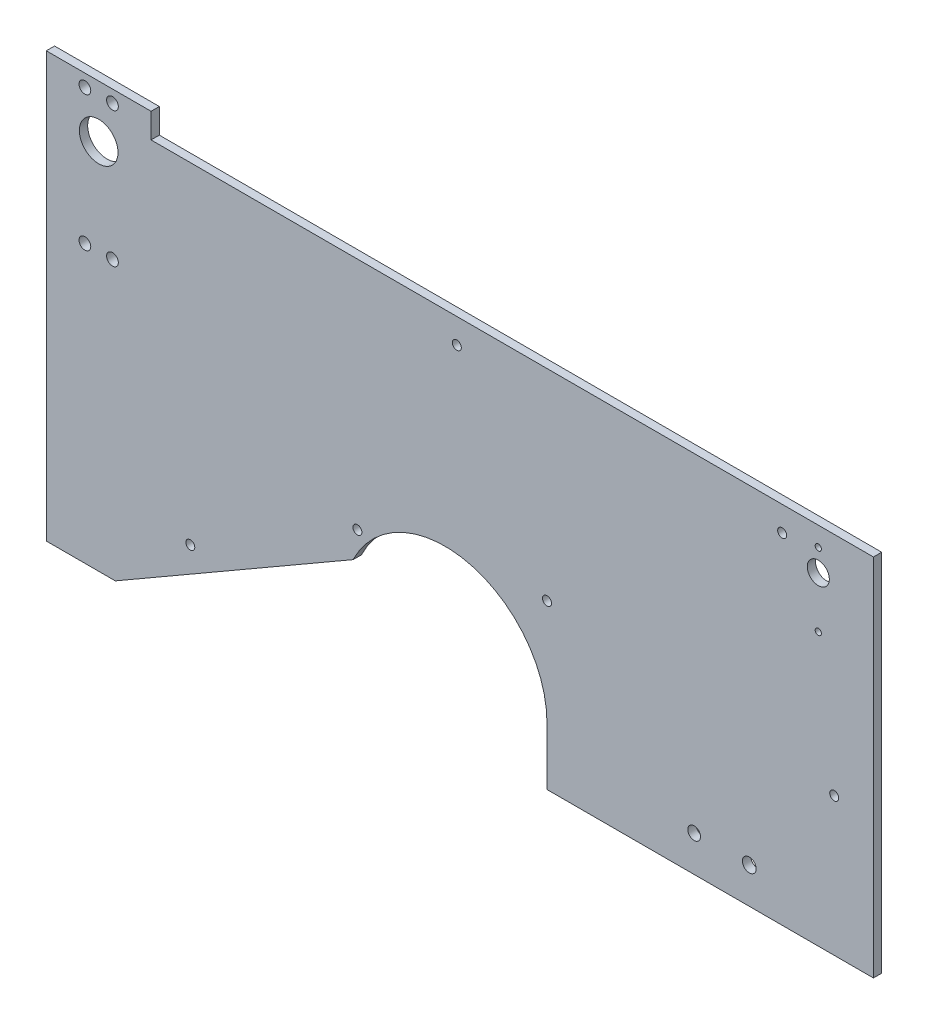
SolidWorks part; units mm, degrees
ref_plane "Front Plane" through (0, 0, 0) normal (0, 0, 1) x (1, 0, 0)
ref_plane "Top Plane" through (0, 0, 0) normal (0, 1, 0) x (1, 0, 0)
ref_plane "Right Plane" through (0, 0, 0) normal (1, 0, 0) x (0, 0, -1)
sketch "Sketch2" plane through (0, 0, 0) normal (0, 0, 1) x (1, 0, 0)
  line L0 (25.0304, 0) -> (111.2865, 49.8)
  line L1 (0, 0) -> (25.0304, 0)
  line L2 (0, 0) -> (0, 154)
  line L4 (300, 0) -> (300, 145)
  line L5 (181.6, 33.7) -> (181.6, 0)
  line L6 (181.6, 0) -> (300, 0)
  line L7 (19, 135) -> (19, 164.3674) construction
  line L11 (38, 145) -> (300, 145)
  line L12 (0, 154) -> (19, 154)
  line L13 (19, 154) -> (38, 154)
  line L14 (38, 154) -> (38, 145)
  line L15 (19, 135) -> (50019, 135) construction
  line L20 (19, 135) -> (19, -49865) construction
  line L21 (24, 149.5) -> (24, -49850.5) construction
  line L22 (14, 149.5) -> (14, -49850.5) construction
  circle A0 centre (19, 135) radius 7
  arc A1 (181.6, 33.7) -> (111.2865, 49.8) centre (144.6, 33.7) ccw
  circle A2 centre (14, 149.5) radius 2.125
  circle A3 centre (24, 149.5) radius 2.125
  circle A4 centre (24, 100.5) radius 2.125
  circle A5 centre (14, 100.5) radius 2.125
  point P19 (19, 154)
  dimension "D3" = 135
  dimension "D4" = 19
  dimension "D5" = 14
  dimension "D6" = 74
  dimension "D7" = 155.4
  dimension "D8" = 33.7
  dimension "D13" = 4.25
  dimension "D14" = 5
  dimension "D15" = 14.5
  dimension "D17" = 49
  dimension "D18" = 4.25
  dimension "D19" = 49
  dimension "D20" = 4.25
  dimension "D1" = 300
  dimension "D2" = 154
  dimension "D9" = 30
  dimension "D10" = 99.6
  dimension "D11" = 19
  dimension "D12" = 145
  dimension "D16" = 9
extrude "Boss-Extrude2" add sketch "Sketch2" along normal blind 3
sketch "Sketch3" plane through (0, 0, 3) normal (0, 0, 1) x (1, 0, 0)
  line L0 (300, 0) -> (300, 145) construction
  line L1 (181.6, 0) -> (300, 0)
  line L2 (181.6, 0) -> (181.6, 12.75)
  line L3 (181.6, 12.75) -> (300, 12.75)
  line L4 (300, 0) -> (300, 12.75)
  dimension "D1" = 12.75
extrude "Cut-Extrude1" cut sketch "Sketch3" against normal through all
sketch "Sketch4" plane through (0, 0, 3) normal (0, 0, 1) x (1, 0, 0)
  line L0 (19, 135) -> (19, -49865) construction
  line L1 (19, 135) -> (-49981, 135) construction
sketch "Sketch5" plane through (0, 0, 3) normal (0, 0, 1) x (1, 0, 0)
  line L0 (300, 12.75) -> (300, 145) construction
  line L1 (300, 12.75) -> (181.6, 12.75) construction
  line L2 (300, 145) -> (38, 145) construction
  line L3 (0, 154) -> (0, 0) construction
  line L4 (0, 0) -> (25.0304, 0) construction
  circle A0 centre (254.98, 25.75) radius 2.5
  circle A1 centre (234.98, 25.75) radius 2.3061
  circle A2 centre (280, 130) radius 4
  circle A3 centre (280, 138) radius 1.125
  circle A4 centre (280, 111.5) radius 1.125
  circle A7 centre (285.78, 62.92) radius 1.625
  circle A8 centre (181.6, 72.03) radius 1.625
  circle A9 centre (52.23, 24.91) radius 1.625
  circle A10 centre (112.84, 59.93) radius 1.625
  circle A11 centre (266.895, 135.995) radius 1.625
  circle A12 centre (148.895, 135.995) radius 1.625
  dimension "D1" = 45.02
  dimension "D2" = 13
  dimension "D3" = 20
  dimension "D4" = 13
  dimension "D5" = 4.6121
  dimension "D6" = 5
  dimension "D7" = 8
  dimension "D8" = 15
  dimension "D9" = 2.25
  dimension "D10" = 8
  dimension "D11" = 18.5
  dimension "D12" = 2.25
  dimension "D13" = 20
  dimension "D14" = 20
  dimension "D15" = 20
  dimension "D16" = 82.08
  dimension "D17" = 3.25
  dimension "D18" = 14.22
  dimension "D19" = 72.97
  dimension "D20" = 3.25
  dimension "D21" = 118.4
  dimension "D22" = 3.25
  dimension "D23" = 52.23
  dimension "D24" = 24.91
  dimension "D25" = 3.25
  dimension "D26" = 112.84
  dimension "D27" = 59.93
  dimension "D28" = 3.25
  dimension "D29" = 9.005
  dimension "D30" = 33.105
  dimension "D31" = 3.25
  dimension "D32" = 118
  dimension "D33" = 9.005
  dimension "D34" = 26.5
extrude "Cut-Extrude2" cut sketch "Sketch5" against normal through all
